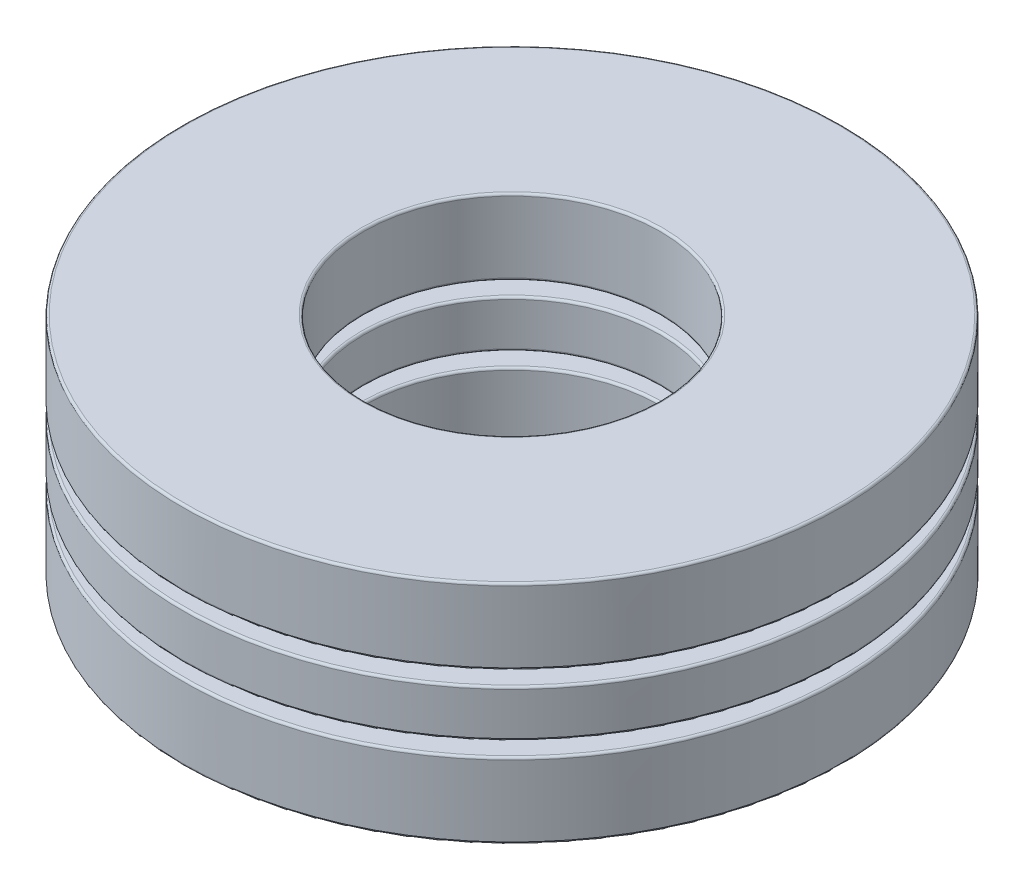
SolidWorks part; units mm, degrees
material "AISI 316 Annealed Stainless Steel Bar (SS)"
ref_plane "Front Plane" through (0, 0, 0) normal (0, 0, 1) x (1, 0, 0)
ref_plane "Top Plane" through (0, 0, 0) normal (0, 1, 0) x (1, 0, 0)
ref_plane "Right Plane" through (0, 0, 0) normal (1, 0, 0) x (0, 0, -1)
sketch "Sketch1" plane through (0, 0, 0) normal (1, 0, 0) x (0, 0, -1)
  line L0 (-7.1437, 0) -> (7.1437, 0) construction
  line L1 (0, -2.4511) -> (0, 2.4511) construction
  line L2 (-7.1437, 0.5106) -> (-3.2131, 0.5106)
  line L3 (-7.1437, 0.5106) -> (-7.1437, -0.5106)
  line L4 (-7.1437, -0.5106) -> (-3.2131, -0.5106)
  line L5 (-3.2131, 0.5106) -> (-3.2131, -0.5106)
  line L6 (-5.1784, 0.817) -> (-5.1784, -0.817) construction
  circle A0 centre (-5.1784, 0) radius 0.817 construction
  point P13 (-5.1784, 0.5106)
  dimension "OD" = 14.2875
  dimension "Shaft Dia" = 6.4262
  dimension "Th" = 4.9022
  dimension "D1" = 1.6341
  dimension "D2" = 1.0213
revolve "Revolve1" add sketch "Sketch1" angle 360 about L1
sketch "Sketch3" plane through (0, 0, 0) normal (1, 0, 0) x (0, 0, -1)
  line L0 (-5.1784, 0.817) -> (-5.1784, -0.817)
  arc A0 (-5.1784, 0.817) -> (-5.1784, -0.817) centre (-5.1784, 0) ccw
  circle A1 centre (-5.1784, 0) radius 0.817 construction
revolve "Cut-Revolve1" cut sketch "Sketch3" angle 360 about L0
sketch "Sketch2" plane through (0, 0, 0) normal (1, 0, 0) x (0, 0, -1)
  line L0 (-5.1784, 0.817) -> (-5.1784, -0.817)
  arc A0 (-5.1784, 0.817) -> (-5.1784, -0.817) centre (-5.1784, 0) ccw
  circle A2 centre (-5.1784, 0) radius 0.817 construction
revolve "Revolve2" add sketch "Sketch2" angle 360 about L0
ref_axis "Axis1" through (0, 2.4511, 0) along (0, -1, 0)
pattern_circular "CirPattern1" count 3 every 120 about axis through (0, 2.4511, 0) along (0, -1, 0) of bodies 187
pattern_circular "CirPattern2" count 3 every 120 about axis through (0, 2.4511, 0) along (0, -1, 0) of "Cut-Revolve1"
sketch "Sketch4" plane through (0, 0, 0) normal (1, 0, 0) x (0, 0, -1)
  line L0 (-7.1437, 0.5106) -> (-7.1437, -0.5106) construction
  line L1 (-7.1437, 0.817) -> (-3.2131, 0.817)
  line L2 (-7.1437, 0.817) -> (-7.1437, 2.4511)
  line L3 (-7.1437, 2.4511) -> (-3.2131, 2.4511)
  line L4 (-3.2131, 0.817) -> (-3.2131, 2.4511)
  line L5 (-7.1437, -2.4511) -> (-3.2131, -2.4511)
  line L6 (-7.1437, -2.4511) -> (-7.1437, -0.817)
  line L7 (-7.1437, -0.817) -> (-3.2131, -0.817)
  line L8 (-3.2131, -2.4511) -> (-3.2131, -0.817)
  line L9 (-5.1784, 0.817) -> (-5.1784, -0.817) construction
  line L10 (-3.2131, 0.5106) -> (-3.2131, -0.5106) construction
  line L11 (0, 0) -> (-7.1437, 0) construction
  line L12 (-7.1437, 0) -> (7.1437, 0) construction
  dimension "Ht" = 4.9022
revolve "Revolve3" add sketch "Sketch4" angle 360 about L1
fillet "Fillet1" radius 0.049 4 edges at (0, 0.817, -3.2131) (0, 2.4511, -3.2131) (0, 0.817, -7.1437) (0, 2.4511, -7.1437)
fillet "Fillet2" radius 0.049 4 edges at (0, -0.5106, -3.2131) (0, 0.5106, -3.2131) (0, -0.5106, -7.1437) (0, 0.5106, -7.1437)
fillet "Fillet3" radius 0.049 4 edges at (0, -2.4511, -3.2131) (0, -0.817, -3.2131) (0, -2.4511, -7.1437) (0, -0.817, -7.1437)
equation "\"D1@Sketch1\" = \"Th@Sketch1\"/3"
equation "\"D2@Sketch1\" = \"D1@Sketch1\"*.625"
equation "\"Balls@CirPattern1\" = \"OD@Sketch1\"*5"
equation "\"Angle@CirPattern1\" = 360/\"Balls@CirPattern1\""
equation "\"D1@CirPattern2\" = \"Balls@CirPattern1\""
equation "\"D2@CirPattern2\" = \"Angle@CirPattern1\""
equation "\"D1@Fillet1\" = \"Th@Sketch1\"*.01"
equation "\"D1@Fillet2\" = \"D1@Fillet1\""
equation "\"D1@Fillet3\" = \"D1@Fillet1\""
